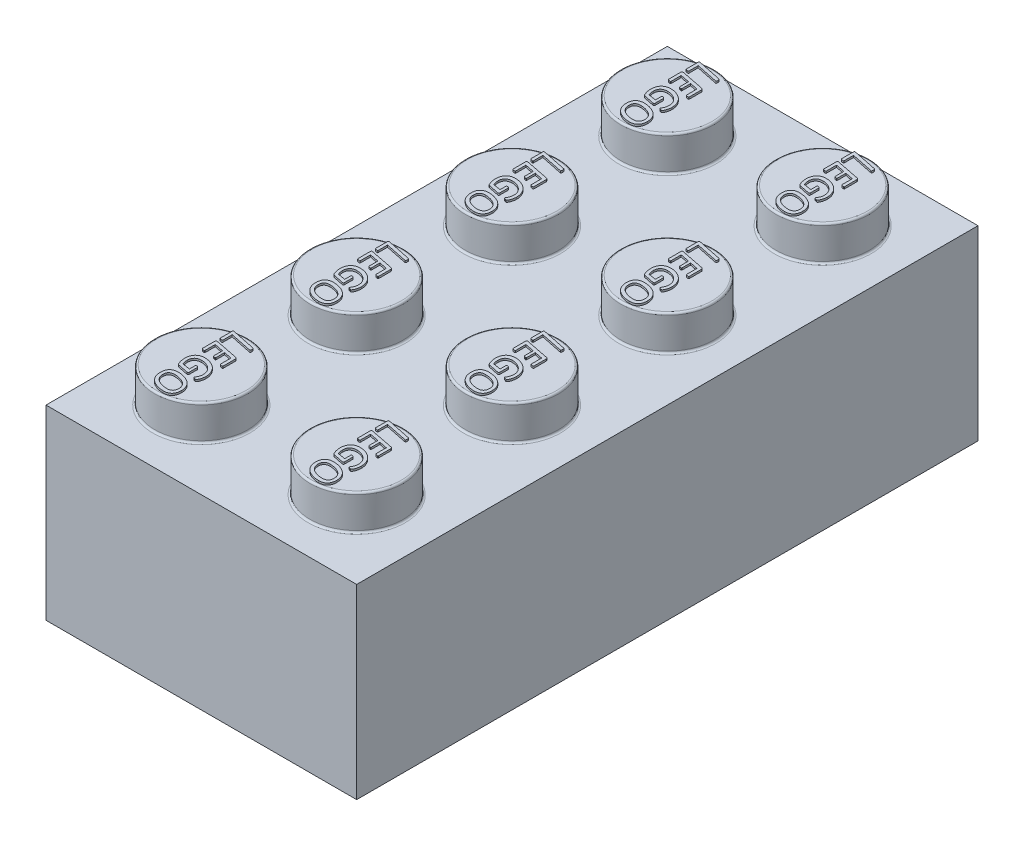
SolidWorks part; units mm, degrees
ref_plane "Front Plane" through (0, 0, 0) normal (0, 0, 1) x (1, 0, 0)
ref_plane "Top Plane" through (0, 0, 0) normal (0, 1, 0) x (1, 0, 0)
ref_plane "Right Plane" through (0, 0, 0) normal (1, 0, 0) x (0, 0, -1)
sketch "Sketch1" plane through (0, 0, 0) normal (0, 1, 0) x (1, 0, 0)
  line L1 (-8, -16) -> (8, -16)
  line L2 (-8, -16) -> (-8, 16)
  line L3 (-8, 16) -> (8, 16)
  line L4 (8, -16) -> (8, 16)
  line L5 (-8, -16) -> (8, 16) construction
  line L6 (-8, 16) -> (8, -16) construction
  point P0 (0, 0)
  dimension "D1" = 16
  dimension "D2" = 32
extrude "Boss-Extrude1" add sketch "Sketch1" along normal blind 9.6
sketch "Sketch2" plane through (0, 9.6, 0) normal (0, 1, 0) x (1, 0, 0)
  line L0 (-8, 16) -> (-4, 16) construction
  line L1 (8, 16) -> (-8, 16) construction
  line L2 (-4, 16) -> (-4, 12) construction
  circle A0 centre (-4, 12) radius 2.4
  dimension "D2" = 4.8
  dimension "D1" = 4
extrude "Boss-Extrude2" add sketch "Sketch2" along normal blind 1.8
sketch "Sketch3" plane through (0, 11.4, 0) normal (0, 1, 0) x (1, 0, 0)
  line L0 (-4.6, 14.3238) -> (-4.6, 9.6762) construction
  line L1 (-1.6, 12) -> (-4.6, 12) construction
  line L2 (-8, 16) -> (-8, -16) construction
  line L3 (8, 16) -> (-8, 16) construction
  circle A0 centre (-4, 12) radius 2.4 construction
  text T0 "LEGO" font "Calibri" height in points 5
  dimension "D1" = 3
extrude "Boss-Extrude3" add sketch "Sketch3" along normal blind 0.1
sketch "Sketch4" plane through (0, 0, 0) normal (0, -1, 0) x (1, 0, 0)
  line L14 (-6.8, -14.8) -> (6.8, -14.8)
  line L15 (6.8, -14.8) -> (6.8, 14.8)
  line L16 (6.8, 14.8) -> (-6.8, 14.8)
  line L17 (-6.8, 14.8) -> (-6.8, -14.8)
  line L18 (-6.8, -14.8) -> (6.8, -14.8)
  line L19 (6.8, -14.8) -> (6.8, 14.8)
  line L20 (6.8, 14.8) -> (-6.8, 14.8)
  line L21 (-6.8, 14.8) -> (-6.8, -14.8)
  dimension "D1" = 1.2
extrude "Cut-Extrude1" cut sketch "Sketch4" against normal offset from surface (8.4 mm away) 1.2 up to face at (-4, 9.6, -14.4)
sketch "Sketch5" plane through (0, 8.4, 0) normal (0, -1, 0) x (1, 0, 0)
  circle A0 centre (-4, -12) radius 2.4 construction
  circle A1 centre (-4, -12) radius 2.4 construction
  circle A2 centre (-4, -12) radius 1
  dimension "D1" = 1.4
extrude "Cut-Extrude2" cut sketch "Sketch5" against normal offset from surface (1.8 mm away) 1.2 up to face at (-3.9406, 11.4, -10.3671)
fillet "Fillet1" radius 0.1 3 edges at (-4, 8.4, -13) (-4, 11.4, -9.6) (-4, 9.6, -14.4)
pattern_linear "LPattern1" count 4 spacing 8 along (0, 0, 1) count 2 spacing 8 along (1, 0, 0) of "Boss-Extrude2", "Boss-Extrude3", "Cut-Extrude2", "Fillet1"
sketch "Sketch6" plane through (0, 8.4, 0) normal (0, -1, 0) x (1, 0, 0)
  line L0 (-4, -13.1) -> (-4, -14.8) construction
  line L1 (6.8, -14.8) -> (-6.8, -14.8) construction
  line L2 (-5.1, -12) -> (-6.8, -12) construction
  line L3 (-6.8, -14.8) -> (-6.8, 14.8) construction
  line L4 (-4, -4) -> (-5.1, -4) construction
  line L5 (-5.1, -4) -> (-6.8, -4) construction
  line L6 (-4, 4) -> (-5.1, 4) construction
  line L7 (-5.1, 4) -> (-6.8, 4) construction
  line L8 (-4, 12) -> (-5.1, 12) construction
  line L9 (-5.1, 12) -> (-6.8, 12) construction
  line L10 (-4, 12) -> (-4, 13.1) construction
  line L11 (-4, 13.1) -> (-4, 14.8) construction
  line L12 (-6.8, 14.8) -> (6.8, 14.8) construction
  line L14 (-7.1, 12.3) -> (-6.5, 12.3)
  line L15 (-7.1, 12.3) -> (-7.1, 11.7)
  line L16 (-7.1, 11.7) -> (-6.5, 11.7)
  line L17 (-6.5, 12.3) -> (-6.5, 11.7)
  line L18 (-7.1, 12.3) -> (-6.5, 11.7) construction
  line L19 (-7.1, 11.7) -> (-6.5, 12.3) construction
  line L20 (-4.3, 15.1) -> (-3.7, 15.1)
  line L21 (-4.3, 15.1) -> (-4.3, 14.5)
  line L22 (-4.3, 14.5) -> (-3.7, 14.5)
  line L23 (-3.7, 15.1) -> (-3.7, 14.5)
  line L24 (-4.3, 15.1) -> (-3.7, 14.5) construction
  line L25 (-4.3, 14.5) -> (-3.7, 15.1) construction
  line L26 (-7.1, 4.3) -> (-6.5, 4.3)
  line L27 (-7.1, 4.3) -> (-7.1, 3.7)
  line L28 (-7.1, 3.7) -> (-6.5, 3.7)
  line L29 (-6.5, 4.3) -> (-6.5, 3.7)
  line L30 (-7.1, 4.3) -> (-6.5, 3.7) construction
  line L31 (-7.1, 3.7) -> (-6.5, 4.3) construction
  line L32 (-7.1, -4.3) -> (-6.5, -4.3)
  line L33 (-7.1, -4.3) -> (-7.1, -3.7)
  line L34 (-7.1, -3.7) -> (-6.5, -3.7)
  line L35 (-6.5, -4.3) -> (-6.5, -3.7)
  line L36 (-7.1, -4.3) -> (-6.5, -3.7) construction
  line L37 (-7.1, -3.7) -> (-6.5, -4.3) construction
  line L38 (-7.1, -12.3) -> (-6.5, -12.3)
  line L39 (-7.1, -12.3) -> (-7.1, -11.7)
  line L40 (-7.1, -11.7) -> (-6.5, -11.7)
  line L41 (-6.5, -12.3) -> (-6.5, -11.7)
  line L42 (-7.1, -12.3) -> (-6.5, -11.7) construction
  line L43 (-7.1, -11.7) -> (-6.5, -12.3) construction
  line L44 (-4.3, -15.1) -> (-3.7, -15.1)
  line L45 (-4.3, -15.1) -> (-4.3, -14.5)
  line L46 (-4.3, -14.5) -> (-3.7, -14.5)
  line L47 (-3.7, -15.1) -> (-3.7, -14.5)
  line L48 (-4.3, -15.1) -> (-3.7, -14.5) construction
  line L49 (-4.3, -14.5) -> (-3.7, -15.1) construction
  circle A0 centre (-4, -12) radius 1.1 construction
  circle A1 centre (-4, -4) radius 1.1 construction
  circle A2 centre (-4, 4) radius 1.1 construction
  circle A3 centre (-4, 12) radius 1.1 construction
  dimension "D1" = 0.6
extrude "Boss-Extrude4" add sketch "Sketch6" along normal up to surface (8.4 mm away) up to face at (0, 0, 0)
sketch "Sketch7" plane through (0, 8.4, 0) normal (0, -1, 0) x (1, 0, 0)
  line L0 (-4, -12) -> (4, -4) construction
  line L1 (4, -4) -> (-4, 4) construction
  line L2 (-4, 4) -> (4, 12) construction
  circle A0 centre (0, -8) radius 2.4
  circle A1 centre (0, 0) radius 2.4
  circle A2 centre (0, 8) radius 2.4
  circle A3 centre (0, 8) radius 3
  circle A4 centre (0, 0) radius 3
  circle A5 centre (0, -8) radius 3
  dimension "D1" = 4.8
  dimension "D2" = 0.6
extrude "Boss-Extrude5" add sketch "Sketch7" along normal up to surface (8.4 mm away) up to face at (-4.9429, 0, 0)
sketch "Sketch8" plane through (0, 8.4, 0) normal (0, -1, 0) x (1, 0, 0)
  line L0 (0, -5) -> (0, -3) construction
  line L1 (0, 3) -> (0, 5) construction
  line L3 (-0.3, -5.25) -> (0.3, -5.25)
  line L4 (-0.3, -5.25) -> (-0.3, -2.75)
  line L5 (-0.3, -2.75) -> (0.3, -2.75)
  line L6 (0.3, -5.25) -> (0.3, -2.75)
  line L7 (-0.3, -5.25) -> (0.3, -2.75) construction
  line L8 (-0.3, -2.75) -> (0.3, -5.25) construction
  line L9 (-0.3, 5.3232) -> (0.3, 5.3232)
  line L10 (-0.3, 5.3232) -> (-0.3, 2.6768)
  line L11 (-0.3, 2.6768) -> (0.3, 2.6768)
  line L12 (0.3, 5.3232) -> (0.3, 2.6768)
  line L13 (-0.3, 5.3232) -> (0.3, 2.6768) construction
  line L14 (-0.3, 2.6768) -> (0.3, 5.3232) construction
  circle A0 centre (0, -8) radius 3 construction
  circle A1 centre (0, 0) radius 3 construction
  circle A2 centre (0, 8) radius 3 construction
  point P11 (0, -4)
  point P16 (0, 4)
  dimension "D1" = 2.5
  dimension "D2" = 0.6
extrude "Boss-Extrude6" add sketch "Sketch8" along normal blind 6
sketch "Sketch9" plane through (0, 8.4, 0) normal (0, -1, 0) x (1, 0, 0)
  line L0 (-3, 0) -> (-6.8, 0) construction
  line L1 (-6.8, -3.7) -> (-6.8, 3.7) construction
  line L3 (-7.3, 0.3) -> (-2.5, 0.3)
  line L4 (-7.3, 0.3) -> (-7.3, -0.3)
  line L5 (-7.3, -0.3) -> (-2.5, -0.3)
  line L6 (-2.5, 0.3) -> (-2.5, -0.3)
  line L7 (-7.3, 0.3) -> (-2.5, -0.3) construction
  line L8 (-7.3, -0.3) -> (-2.5, 0.3) construction
  arc A0 (-0.3, 2.985) -> (-0.3, -2.985) centre (0, 0) ccw construction
  point P7 (-4.9, 0)
  dimension "D1" = 0.6
  dimension "D2" = 4.8
extrude "Boss-Extrude7" add sketch "Sketch9" along normal blind 4
mirror "Mirror1" about plane through (0, 0, 0) normal (1, 0, 0) of "Boss-Extrude7", "Boss-Extrude4"
fillet "Fillet2" radius 0.1 92 edges at (-6.65, 0, -4.3) (-6.65, 0, -11.7) (-6.65, 0, -3.7) (-6.65, 0, 3.7) (-6.65, 0, 11.7) (-6.65, 0, 4.3) (-6.65, 0, 12.3) (-4.3, 0, 14.65) (-3.7, 0, 14.65) (3.7, 0, 14.65) (4.3, 0, 14.65) (6.65, 0, 12.3) (6.65, 0, 11.7) (6.65, 0, 4.3) (6.65, 0, 3.7) (6.65, 0, -3.7) (6.65, 0, -4.3) (6.65, 0, -11.7) (6.65, 0, -12.3) (4.3, 0, -14.65) (-3.7, 0, -14.65) (3.7, 0, -14.65) (-4.3, 0, -14.65) (-6.65, 0, -12.3) (-6.8, 0, -8) (-6.8, 4.2, -4.3) (-6.8, 8.4, -8) (-6.8, 4.2, -11.7) (-6.8, 4.4, 0) (-6.8, 6.4, -0.3) (-6.8, 8.4, -2) (-6.8, 4.2, -3.7) (-6.8, 0, 0) (-6.8, 4.2, 3.7) (-6.8, 8.4, 2) (-6.8, 6.4, 0.3) (-6.8, 0, 8) (-6.8, 4.2, 11.7) (-6.8, 8.4, 8) (-6.8, 4.2, 4.3) (-6.8, 0, 13.55) (-6.8, 8.4, 13.55) (-6.8, 4.2, 12.3) (-5.55, 8.4, 14.8) (-6.8, 4.2, 14.8) (-5.55, 0, 14.8) (-4.3, 4.2, 14.8) (-3.7, 4.2, 14.8) (0, 0, 14.8) (3.7, 4.2, 14.8) (0, 8.4, 14.8) (5.55, 8.4, 14.8) (4.3, 4.2, 14.8) (5.55, 0, 14.8) (6.8, 4.2, 14.8) (6.8, 0, 13.55) (6.8, 4.2, 12.3) (6.8, 8.4, 13.55) (6.8, 4.2, 11.7) (6.8, 0, 8) (6.8, 4.2, 4.3) (6.8, 8.4, 8) (6.8, 6.4, 0.3) (6.8, 8.4, 2) (6.8, 4.2, 3.7) (6.8, 0, 0) (6.8, 4.2, -3.7) (6.8, 8.4, -2) (6.8, 6.4, -0.3) (6.8, 4.4, 0) (6.8, 4.2, -4.3) (6.8, 0, -8) (6.8, 4.2, -11.7) (6.8, 8.4, -8) (6.8, 8.4, -13.55) (6.8, 4.2, -12.3) (6.8, 0, -13.55) (6.8, 4.2, -14.8) (5.55, 0, -14.8) (4.3, 4.2, -14.8) (5.55, 8.4, -14.8) (-3.7, 4.2, -14.8) (0, 8.4, -14.8) (3.7, 4.2, -14.8) (0, 0, -14.8) (-5.55, 0, -14.8) (-5.55, 8.4, -14.8) (-4.3, 4.2, -14.8) (-6.8, 8.4, -13.55) (-6.8, 4.2, -14.8) (-6.8, 0, -13.55) (-6.8, 4.2, -12.3)
